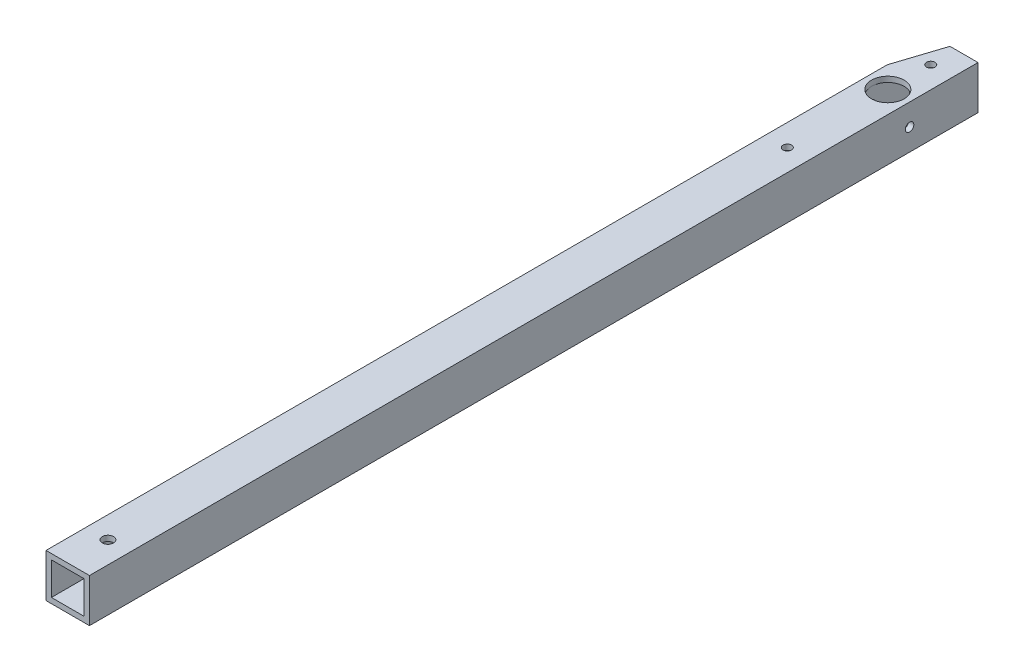
SolidWorks part; units mm, degrees
ref_plane "Front Plane" through (0, 0, 0) normal (0, 0, 1) x (1, 0, 0)
ref_plane "Top Plane" through (0, 0, 0) normal (0, 1, 0) x (1, 0, 0)
ref_plane "Right Plane" through (0, 0, 0) normal (1, 0, 0) x (0, 0, -1)
sketch "Sketch1" plane through (0, 0, 0) normal (0, 0, 1) x (1, 0, 0)
  line L0 (-9.525, 9.525) -> (9.525, 9.525)
  line L2 (-12.7, 12.7) -> (12.7, 12.7)
  line L3 (-12.7, 12.7) -> (-12.7, -12.7)
  line L4 (-12.7, -12.7) -> (12.7, -12.7)
  line L5 (12.7, 12.7) -> (12.7, -12.7)
  line L10 (9.525, 9.525) -> (9.525, -9.525)
  line L11 (-9.525, -9.525) -> (9.525, -9.525)
  line L12 (-9.525, 9.525) -> (-9.525, -9.525)
  point P12 (0, 12.7)
  point P14 (12.7, 0)
  dimension "Wall Thickness" = 3.175
  dimension "Outside Width" = 25.4
  dimension "Outside Height" = 25.4
  dimension "Inside Height" = 19.05
  dimension "Inside Width" = 19.05
sketch "Sketch2" plane through (0, 0, 0) normal (1, 0, 0) x (0, 0, -1)
  line L0 (266.7, 0) -> (-266.7, 0)
  point P4 (0, 0)
  point P7 (-266.7, 0)
  point P10 (266.7, 0)
  dimension "Length" = 533.4
sketch "Sketch3" plane through (0, 0, 0) normal (0, 0, 1) x (1, 0, 0)
  line L21 (12.7, 12.7) -> (-12.7, 12.7)
  line L22 (12.7, -12.7) -> (12.7, 12.7)
  line L23 (-12.7, -12.7) -> (12.7, -12.7)
  line L24 (-12.7, 12.7) -> (-12.7, -12.7)
  line L25 (12.7, 12.7) -> (-12.7, 12.7)
  line L26 (12.7, -12.7) -> (12.7, 12.7)
  line L27 (-12.7, -12.7) -> (12.7, -12.7)
  line L28 (-12.7, 12.7) -> (-12.7, -12.7)
  line L29 (9.525, 9.525) -> (-9.525, 9.525)
  line L30 (9.525, -9.525) -> (9.525, 9.525)
  line L31 (-9.525, -9.525) -> (9.525, -9.525)
  line L32 (-9.525, 9.525) -> (-9.525, -9.525)
  line L33 (9.525, 9.525) -> (-9.525, 9.525)
  line L34 (9.525, -9.525) -> (9.525, 9.525)
  line L35 (-9.525, -9.525) -> (9.525, -9.525)
  line L36 (-9.525, 9.525) -> (-9.525, -9.525)
  dimension "D1" = 0
  dimension "D2" = 0
extrude "Boss-Extrude1" add sketch "Sketch3" along normal up to vertex (266.7 mm away) and the other way up to vertex (266.7 mm away) up to point (0, 0, 266.7) other way up to point (0, 0, -266.7)
sketch "Drawing Reference" plane through (0, 0, 0) normal (1, 0, 0) x (0, 0, -1)
  line L0 (-266.7, 0) -> (266.7, 0) construction
  line L1 (0, -12.7) -> (0, 12.7) construction
  line L2 (-266.7, -12.7) -> (266.7, -12.7) construction
  line L5 (-266.7, 12.7) -> (266.7, 12.7) construction
  point P7 (-248.412, 0)
  point P8 (248.412, 0)
  dimension "D1" = 18.288
sketch "Sketch4" plane through (0, 12.7, 0) normal (0, 1, 0) x (1, 0, 0)
  line L1 (0, 266.7) -> (0, 212.725) construction
  line L7 (-12.7, 225.0135) -> (-12.7, 266.7)
  line L8 (-188.9197, -317.3351) -> (4.6184, 278.3139) construction
  line L10 (-12.7, -266.7) -> (-12.7, 266.7) construction
  line L11 (-12.7, 266.7) -> (12.7, 266.7)
  line L12 (12.7, 266.7) -> (12.7, 252.73)
  line L13 (12.7, -266.7) -> (12.7, 266.7) construction
  line L14 (12.7, 252.73) -> (-3.6943, 252.73)
  line L15 (-3.6943, 252.73) -> (-12.7, 225.0135)
  circle A0 centre (0, 212.725) radius 9.525
  dimension "D1" = 13.97
extrude "Cut-Extrude1" cut sketch "Sketch4" against normal blind 25.4
sketch "Sketch5" plane through (0, -12.7, 0) normal (0, -1, 0) x (1, 0, 0)
  circle A0 centre (-0.3457, -179.775) radius 9.525
extrude "Cut-Extrude2" cut sketch "Sketch5" against normal blind 3.175
sketch "Sketch6" plane through (12.7, 0, 0) normal (1, 0, 0) x (0, 0, -1)
  line L0 (252.73, 0) -> (212.725, 0) construction
  line L1 (252.73, -12.7) -> (252.73, 12.7) construction
hole_wizard "#10 Clearance Hole1" positions "Sketch7" profile "Sketch8" hole size "#10" standard "ANSI Inch" end condition through all
sketch "Sketch7" plane through (12.7, 0, 0) normal (1, 0, 0) x (0, 0, -1)
  point P0 (212.725, 0)
sketch "Sketch8" plane through (12.7, 0, -212.725) normal (0, 1, 0) x (0, 0, -1)
  line L0 (0, 0) -> (0, 25.4)
  line L1 (0, 25.4) -> (2.4892, 25.4)
  line L2 (2.4892, 25.4) -> (2.4892, 0)
  line L5 (2.4892, 0) -> (0, 0)
  line L11 (0, -6.35) -> (0, 107.95) construction
  dimension "Thru Hole Dia." = 4.9784
  dimension "Thru Hole Depth" = 25.4
hole_wizard "#10 Clearance Hole2" positions "Sketch9" profile "Sketch10" hole size "#10" standard "ANSI Inch" end condition through all
sketch "Sketch9" plane through (0, 12.7, 0) normal (0, 1, 0) x (1, 0, 0)
  point P0 (0, 153.96)
  point P3 (0, 237.8065)
sketch "Sketch10" plane through (0, 12.7, -153.96) normal (1, 0, 0) x (0, 0, 1)
  line L0 (0, 0) -> (0, 25.4)
  line L1 (0, 25.4) -> (2.4892, 25.4)
  line L2 (2.4892, 25.4) -> (2.4892, 0)
  line L5 (2.4892, 0) -> (0, 0)
  line L11 (0, -6.35) -> (0, 107.95) construction
  dimension "Thru Hole Dia." = 4.9784
  dimension "Thru Hole Depth" = 25.4
hole_wizard "1/4 Clearance Hole2" positions "Sketch13" profile "Sketch14" hole size "1/4" standard "ANSI Inch" end condition through all
sketch "Sketch13" plane through (0, 12.7, 0) normal (0, 1, 0) x (1, 0, 0)
  point P0 (0, -243.2081)
sketch "Sketch14" plane through (0, 12.7, 243.2081) normal (1, 0, 0) x (0, 0, 1)
  line L0 (0, 0) -> (0, 25.4)
  line L1 (0, 25.4) -> (3.2639, 25.4)
  line L2 (3.2639, 25.4) -> (3.2639, 0)
  line L5 (3.2639, 0) -> (0, 0)
  line L11 (0, -6.35) -> (0, 107.95) construction
  dimension "Thru Hole Dia." = 6.5278
  dimension "Thru Hole Depth" = 25.4
equation "\"D1@Drawing Reference\"=\"Outside Width@Sketch1\" * 0.72"
